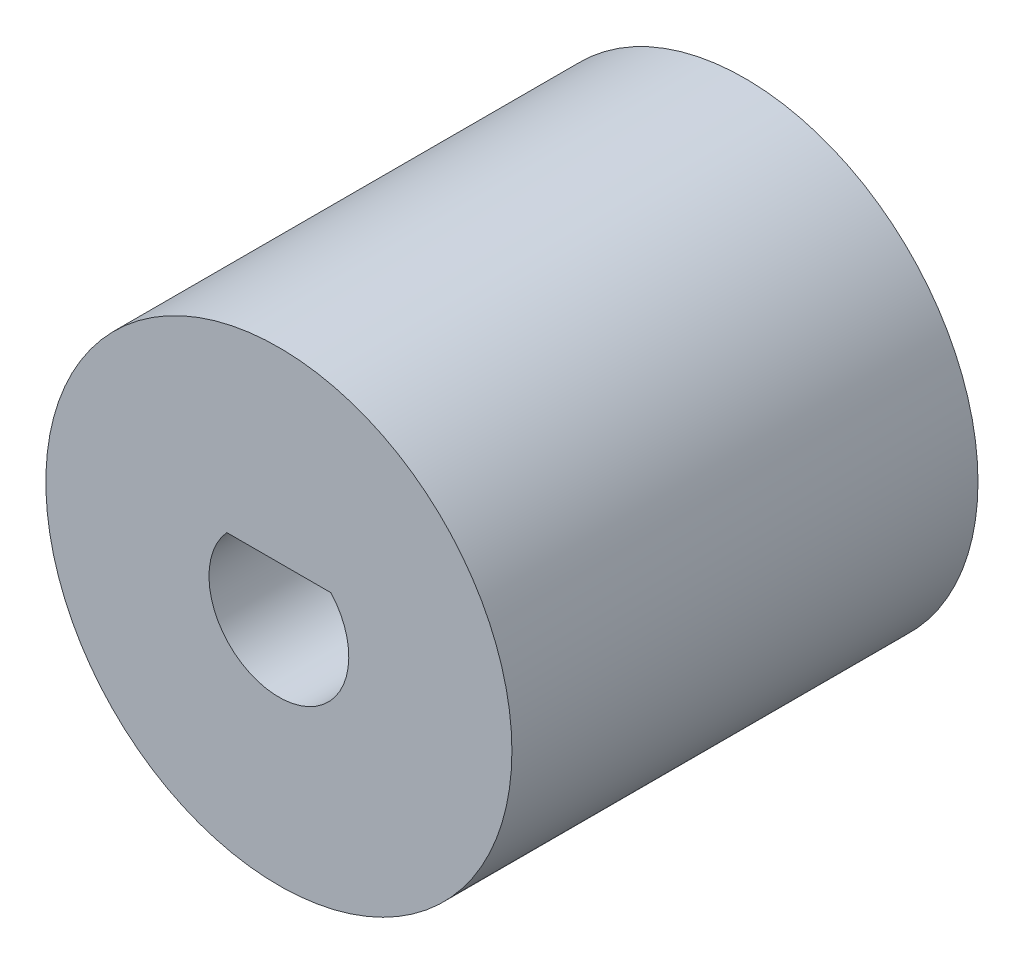
SolidWorks part; units mm, degrees
note: '?' marks a value the reader was unsure of. The reader was unsure of these and kept them because the rebuilt part matched: shared geometry of "Sketch1<5>".
ref_plane "Front Plane" through (0, 0, 0) normal (0, 0, 1) x (1, 0, 0)
ref_plane "Top Plane" through (0, 0, 0) normal (0, 1, 0) x (1, 0, 0)
ref_plane "Right Plane" through (0, 0, 0) normal (1, 0, 0) x (0, 0, -1)
sketch "Sketch1" plane through (0, 0, 0) normal (0, 0, 1) x (1, 0, 0)
  line L0 (-1.118, 1) -> (1.118, 1)
  line L1 (-0.8001, 0.8) -> (-0.8001, 2.2627)
  line L2 (0.7999, 0.8) -> (0.7999, 2.2628)
  line L3 (0.8, 0.8001) -> (2.2627, 0.8001)
  line L4 (0.8, -0.7999) -> (2.2628, -0.7999)
  line L5 (0.8001, -0.8) -> (0.8001, -2.2627)
  line L6 (-0.7999, -0.8) -> (-0.7999, -2.2628)
  line L7 (-0.8, -0.8001) -> (-2.2627, -0.8001)
  line L8 (-0.8, 0.7999) -> (-2.2628, 0.7999)
  line L9 (0, 0) -> (0.7999, 0.8) construction
  line L10 (-0.8001, 0.8) -> (-0.8, 0.7999)
  line L11 (0.8, 0.8001) -> (0.7999, 0.8)
  line L12 (0.8, -0.7999) -> (0.8001, -0.8)
  line L13 (-0.8, -0.8001) -> (-0.7999, -0.8)
  circle A0 centre (0, 0) radius 5
  circle A1 centre (0, 0) radius 1.5
  circle A2 centre (0, 0) radius 2.4
  point P29 (0, 0)
  dimension "D1" = 10
  dimension "D2" = 3
  dimension "D7" = 4.8
  dimension "D3" = 1
  dimension "D5" = 0.8
  dimension "D6" = 0.8001
  dimension "D8" = 0.7999
  dimension "D9" = 0.8
  dimension "D10" = 1.1313
  dimension "D11" = 0.7999
  dimension "D4" = 4
extrude "Boss-Extrude1" add sketch "Sketch1" along normal blind 5 contours A0 A2 | L7 A2 L6 A1 | L6 A2 L5 A1 | L8 A2 L7 A1 | L1 A2 L8 A1 | L2 A2 L1 A1 | L3 A2 L2 A1 | L4 A2 L3 A1 | L5 A2 L4 A1 | L2 A1 L1 L0 | L0 A1 L2 | L1 A1 L0
extrude "Boss-Extrude2" add sketch "Sketch1<5>" against normal blind 5 contours A0 A2 | L5 A2 L4 A1 | L3 A2 L2 A1 | L1 A2 L8 A1 | L7 A2 L6 A1 | L0 A1 L2 | L1 A1 L0 | L0 A1 L8 L10 L1 | L3 A1 L0 L2 L11 | L5 A1 L4 L12 | L7 A1 L6 L13
sketch "Sketch1<5>" plane through (0, 0, 0) normal (0, 0, 1) x (1, 0, 0) same geometry as "Sketch1"
ref_axis "Axis1" through (0, 0, -5.5) along (0, 0, 1)?
